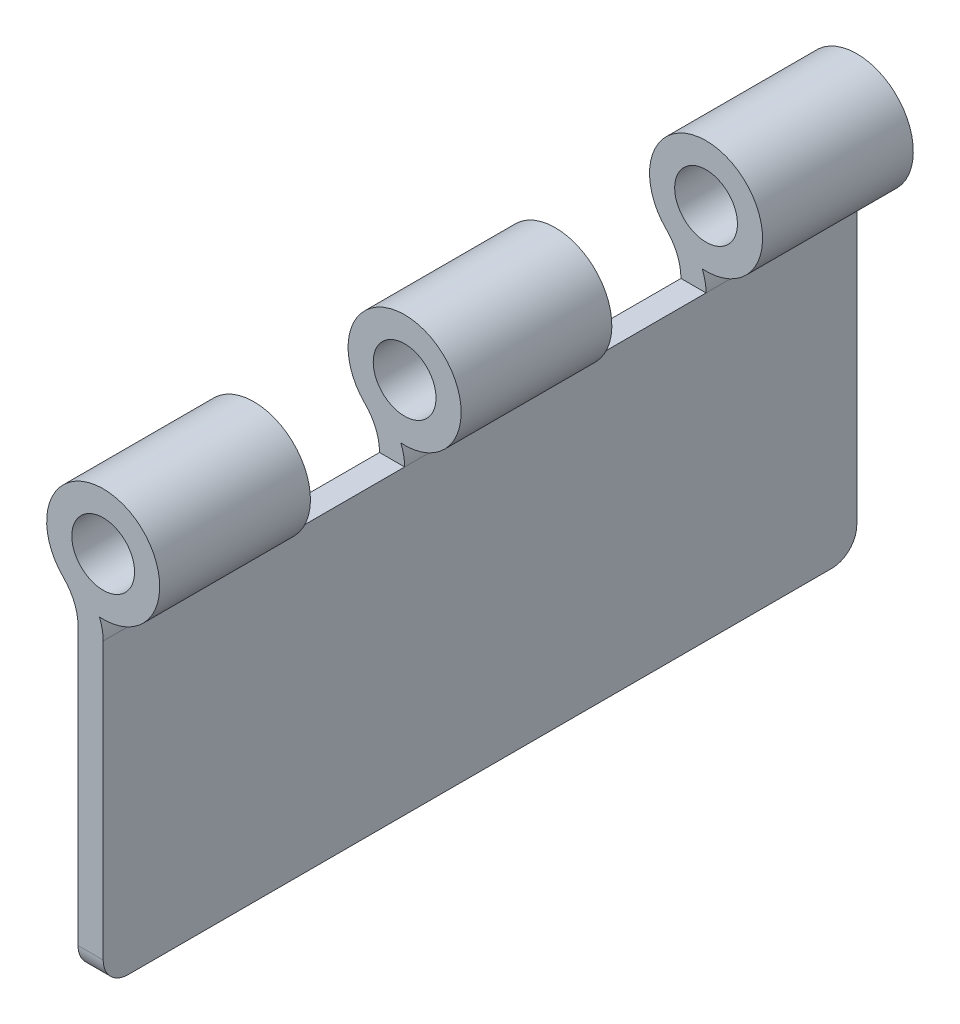
SolidWorks part; units mm, degrees
ref_plane "Front Plane" through (0, 0, 0) normal (0, 0, 1) x (1, 0, 0)
ref_plane "Top Plane" through (0, 0, 0) normal (0, 1, 0) x (1, 0, 0)
ref_plane "Right Plane" through (0, 0, 0) normal (1, 0, 0) x (0, 0, -1)
sketch "Sketch1" plane through (0, 0, 0) normal (0, 0, 1) x (1, 0, 0)
  line L0 (0, 0) -> (-2.54, 0)
  line L1 (-2.54, 0) -> (-2.54, 30.48)
  line L2 (0, 0) -> (0, 30.48)
  circle A0 centre (0, 38.1) radius 5.715
  arc A1 (-2.54, 30.48) -> (-4.0242, 34.042) centre (-7.5565, 30.48) ccw
  arc A2 (0, 30.48) -> (-0.381, 32.3977) centre (-5.0165, 30.48) ccw
  circle A3 centre (0, 38.1) radius 3.175
  dimension "D1" = 11.43
  dimension "D4" = 7.62
  dimension "D5" = 6.35
  dimension "D2" = 2.54
  dimension "D3" = 38.1
extrude "Boss-Extrude1" add sketch "Sketch1" along normal mid plane 76.2 contours L2 A2 A0 A1 L1 L0 | A0 A3 region at (-1.2918, 16.3958, 0) region at (-2.2845, 33.0383, 0)
ref_plane "Plane1" through (0, 0, 15.24) normal (0, 0, 1) x (1, 0, 0)
sketch "Sketch2" plane through (0, 0, 15.24) normal (0, 0, 1) x (1, 0, 0)
  line L0 (0, 30.48) -> (-2.54, 30.48)
  arc A0 (0, 30.48) -> (-0.381, 32.3977) centre (-5.0165, 30.48) ccw construction
  arc A1 (-2.54, 30.48) -> (-4.0242, 34.042) centre (-7.5565, 30.48) ccw construction
  circle A2 centre (0, 38.1) radius 3.175 construction
  arc A3 (-0.381, 32.3977) -> (-4.0242, 34.042) centre (0, 38.1) ccw construction
  arc A4 (0, 30.48) -> (-0.381, 32.3977) centre (-5.0165, 30.48) ccw
  arc A5 (-2.54, 30.48) -> (-4.0242, 34.042) centre (-7.5565, 30.48) ccw
  circle A6 centre (0, 38.1) radius 3.175
  arc A7 (-0.381, 32.3977) -> (-4.0242, 34.042) centre (0, 38.1) ccw
extrude "Cut-Extrude1" cut sketch "Sketch2" against normal mid plane 15.24 contours A4 A7 A5 L0 A6 region at (-1.27, 30.6556, 15.24)
mirror "Mirror1" about plane through (0, 0, 0) normal (0, 0, 1) of "Cut-Extrude1"
fillet "Fillet1" radius 2.54 2 edges at (-1.27, 0, -38.1) (-1.27, 0, 38.1)
